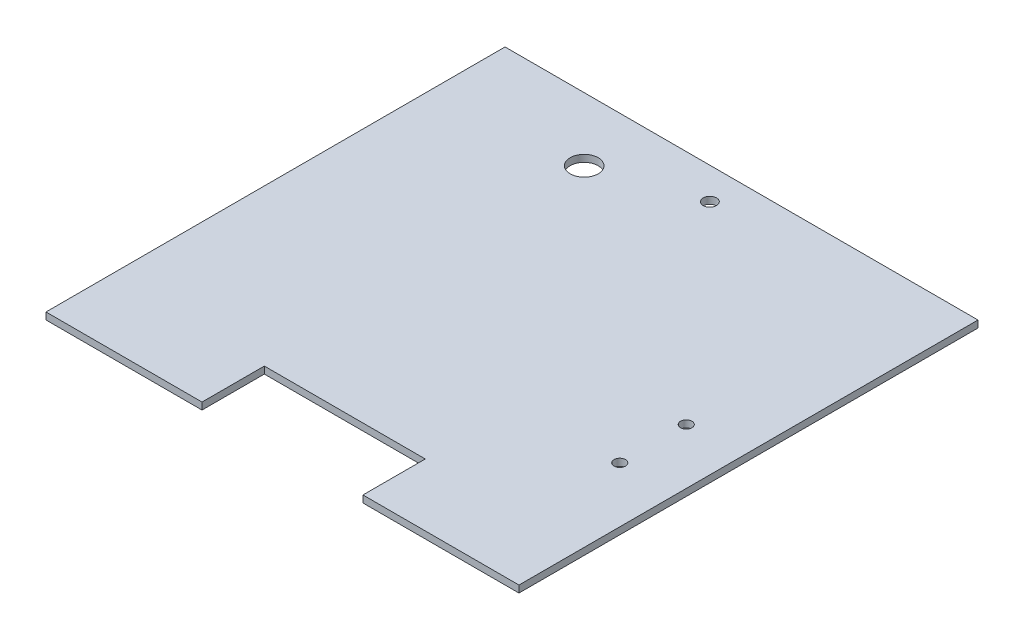
SolidWorks part; units mm, degrees
ref_plane "Front Plane" through (0, 0, 0) normal (0, 0, 1) x (1, 0, 0)
ref_plane "Top Plane" through (0, 0, 0) normal (0, 1, 0) x (1, 0, 0)
ref_plane "Right Plane" through (0, 0, 0) normal (1, 0, 0) x (0, 0, -1)
sketch "Sketch1" plane through (0, 0, 0) normal (0, 1, 0) x (1, 0, 0)
  line L1 (-94.869, -92.075) -> (94.869, -92.075)
  line L2 (-94.869, -92.075) -> (-94.869, 92.075)
  line L3 (-94.869, 92.075) -> (94.869, 92.075)
  line L4 (94.869, -92.075) -> (94.869, 92.075)
  line L5 (-94.869, -92.075) -> (94.869, 92.075) construction
  line L6 (-94.869, 92.075) -> (94.869, -92.075) construction
  point P0 (0, 0)
  dimension "D1" = 189.738
  dimension "D2" = 184.15
extrude "Boss-Extrude1" add sketch "Sketch1" along normal blind 2.794
sketch "Sketch2" plane through (0, 2.794, 0) normal (0, 1, 0) x (1, 0, 0)
  line L2 (94.869, 92.075) -> (-94.869, 92.075) construction
  circle A0 centre (0, 79.375) radius 2.6797
  dimension "D1" = 5.3594
  dimension "D2" = 12.7
extrude "Cut-Extrude1" cut sketch "Sketch2" against normal through all
sketch "Sketch3" plane through (0, 2.794, 0) normal (0, 1, 0) x (1, 0, 0)
  line L0 (0, -92.075) -> (-32.28, -92.075)
  line L1 (-94.869, -92.075) -> (94.869, -92.075) construction
  line L2 (-32.28, -92.075) -> (-32.28, -67.075)
  line L3 (-32.28, -67.075) -> (32.28, -67.075)
  line L4 (32.28, -67.075) -> (32.28, -92.075)
  line L5 (32.28, -92.075) -> (0, -92.075)
  point P5 (0, -67.075)
  dimension "D1" = 64.56
  dimension "D3" = 25
extrude "Cut-Extrude2" cut sketch "Sketch3" against normal through all
sketch "Sketch5" plane through (0, 2.794, 0) normal (0, 1, 0) x (1, 0, 0)
  line L4 (36.703, 15.8242) -> (82.169, 15.8242)
  line L5 (82.169, 15.8242) -> (82.169, -47.4726)
  line L6 (82.169, -47.4726) -> (36.703, -47.4726)
  line L7 (36.703, -47.4726) -> (36.703, 15.8242)
  line L8 (94.869, -92.075) -> (94.869, 92.075) construction
  line L10 (94.869, 92.075) -> (-94.869, 92.075) construction
  line L15 (-94.869, 92.075) -> (-94.869, -92.075) construction
  line L17 (-50.419, 92.075) -> (-25.019, 92.075)
  line L18 (-50.419, 92.075) -> (-50.419, 79.375)
  line L19 (-50.419, 79.375) -> (-25.019, 79.375)
  line L20 (-25.019, 92.075) -> (-25.019, 79.375)
  circle A2 centre (72.644, -2.7436) radius 2.286
  circle A3 centre (72.644, -29.4136) radius 2.286
  circle A4 centre (-37.719, 66.675) radius 5.6134
  point P22 (-37.719, 79.375)
  dimension "D3" = 47.4726
  dimension "D5" = 57.15
  dimension "D6" = 11.2268
  dimension "D7" = 25.4
  dimension "D10" = 4.572
  dimension "D11" = 18.059
  dimension "D12" = 26.67
  dimension "D13" = 18.5678
  dimension "D14" = 9.525
  dimension "D15" = 12.7
  dimension "D4" = 25.4
  dimension "D2" = 12.7
  dimension "D8" = 45.466
  dimension "D9" = 63.2968
extrude "Cut-Extrude3" cut sketch "Sketch5" against normal through all contours A2 | A4 | A3
